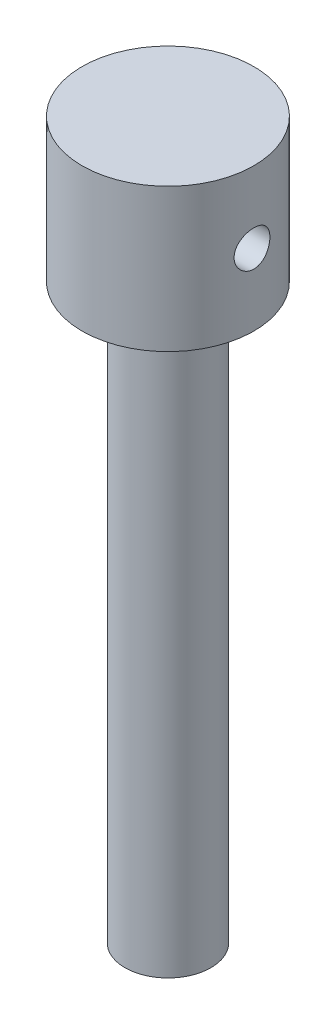
SolidWorks part; units mm, degrees
material "1060 Alloy"
ref_plane "Front Plane" through (0, 0, 0) normal (0, 0, 1) x (1, 0, 0)
ref_plane "Top Plane" through (0, 0, 0) normal (0, 1, 0) x (1, 0, 0)
ref_plane "Right Plane" through (0, 0, 0) normal (1, 0, 0) x (0, 0, -1)
sketch "Sketch2" plane through (0, 0, 0) normal (0, 1, 0) x (1, 0, 0)
  circle A0 centre (0, 0) radius 12
  circle A1 centre (0, 0) radius 6
  dimension "D1" = 24
  dimension "D2" = 12
extrude "Boss-Extrude2" add sketch "Sketch2" against normal blind 20
extrude "Boss-Extrude3" add sketch "Sketch2<2>" against normal blind 100 contours A1
sketch "Sketch2<2>" plane through (0, 0, 0) normal (0, 1, 0) x (1, 0, 0) same geometry as "Sketch2"
sketch "Sketch3" plane through (0, 0, 0) normal (1, 0, 0) x (0, 0, -1)
  line L0 (12, 0) -> (-12, 0) construction
  line L1 (12, -20) -> (12, 0) construction
  circle A0 centre (0, -10) radius 2.5
  dimension "D3" = 5
  dimension "D1" = 10
  dimension "D2" = 12
extrude "Cut-Extrude1" cut sketch "Sketch3" against normal through all and the other way through all
